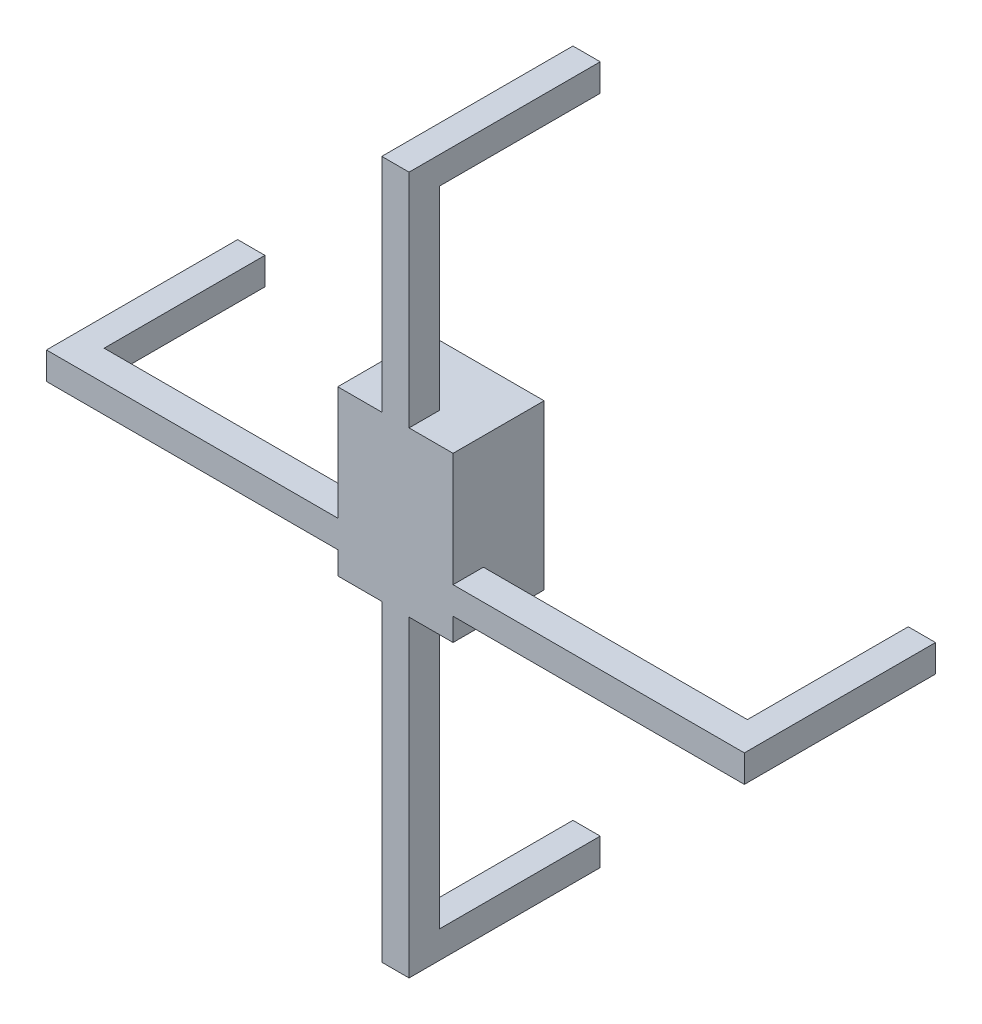
SolidWorks part; units mm, degrees
ref_plane "Front Plane" through (0, 0, 0) normal (0, 0, 1) x (1, 0, 0)
ref_plane "Top Plane" through (0, 0, 0) normal (0, 1, 0) x (1, 0, 0)
ref_plane "Right Plane" through (0, 0, 0) normal (1, 0, 0) x (0, 0, -1)
sketch "Sketch6" plane through (0, 0, 0) normal (1, 0, 0) x (0, 0, -1)
  line L0 (-4, 2.5) -> (1, 2.5) construction
  line L1 (27.5, 55.5) -> (1, 55.5)
  line L3 (-4, -55) -> (27.5, -55)
  line L4 (27.5, -55) -> (27.5, -50.5)
  line L5 (27.5, -50.5) -> (1, -50.5)
  line L8 (27.5, 60) -> (27.5, 55.5)
  line L10 (1, -50.5) -> (1, 55.5)
  line L12 (-4, -55) -> (-4, 60)
  line L22 (-4, 60) -> (27.5, 60)
  dimension "D3" = 5
  dimension "D6" = 4.5
ref_plane "Plane2" through (0, 2.5, 0) normal (0, 1, 0) x (1, 0, 0)
sketch "Sketch8" plane through (0, 2.5, 0) normal (0, 1, 0) x (1, 0, 0)
  line L0 (-57.5, -4) -> (57.5, -4)
  line L1 (-53, 1) -> (53, 1)
  line L3 (57.5, -4) -> (57.5, 27.5)
  line L11 (53, 27.5) -> (57.5, 27.5)
  line L12 (0, -4) -> (0, 1) construction
  line L13 (53, 27.5) -> (53, 1)
  line L14 (-53, 27.5) -> (-53, 1)
  line L15 (-53, 27.5) -> (-57.5, 27.5)
  line L16 (-57.5, -4) -> (-57.5, 27.5)
  point P0 (10.2551, -12.9586)
  point P2 (-10.2551, -12.9586)
  dimension "D2" = 4.5
  dimension "D9" = 5
extrude "Boss-Extrude7" add sketch "Sketch8" along normal blind 2.25 and the other way blind 2.25
sketch "Sketch10" plane through (0, 0, -1) normal (0, 0, -1) x (-1, 0, 0)
  line L2 (6.5, 20.5) -> (-6.5, 20.5)
  line L3 (6.5, 20.5) -> (6.5, -2.5)
  line L4 (-6.5, 20.5) -> (-6.5, -2.5)
  line L7 (6.5, -2.5) -> (6.5, -3.5)
  line L8 (-6.5, -2.5) -> (-6.5, -3.5)
  line L10 (9.5, -2.5) -> (9.5, -3.5)
  line L11 (9.5, 23.5) -> (9.5, -2.5)
  line L12 (9.5, 23.5) -> (-9.5, 23.5)
  line L13 (-9.5, 23.5) -> (-9.5, -2.5)
  line L14 (-9.5, -2.5) -> (-9.5, -3.5)
  line L15 (9.5, -3.5) -> (6.5, -3.5)
  line L16 (-9.5, -3.5) -> (-6.5, -3.5)
  point P6 (0, 1)
  dimension "D1" = 23
  dimension "D2" = 13
  dimension "D3" = 3
extrude "Boss-Extrude10" add sketch "Sketch10" along normal blind 10
extrude "Boss-Extrude12" add sketch "Sketch6" along normal blind 2.25 and the other way blind 2.25
sketch "Sketch11" plane through (0, 0, -1) normal (0, 0, 1) x (1, 0, 0)
  line L1 (-9.5, 23.5) -> (9.5, 23.5)
  line L2 (-9.5, 23.5) -> (-9.5, -3.5)
  line L3 (-9.5, -3.5) -> (9.5, -3.5)
  line L4 (9.5, 23.5) -> (9.5, -3.5)
extrude "Boss-Extrude13" add sketch "Sketch11" along normal up to surface (5 mm away) up to face at (0, 2.5, 4)
